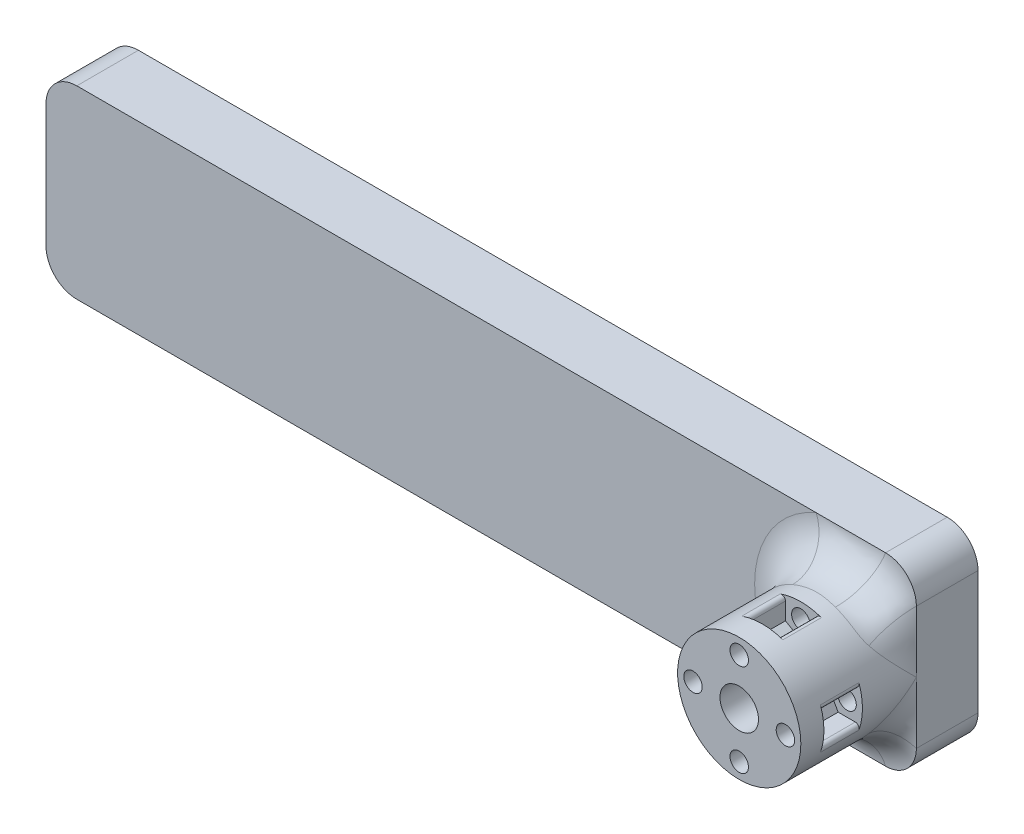
SolidWorks part; units mm, degrees
ref_plane "正面" through (0, 0, 0) normal (0, 0, 1) x (1, 0, 0)
ref_plane "平面" through (0, 0, 0) normal (0, 1, 0) x (1, 0, 0)
ref_plane "右側面" through (0, 0, 0) normal (1, 0, 0) x (0, 0, -1)
sketch "ｽｹｯﾁ1" plane through (0, 0, 0) normal (0, 0, 1) x (1, 0, 0)
  circle A1 centre (0, 0) radius 8
  dimension "D1" = 16
extrude "ﾎﾞｽ - 押し出し1" add sketch "ｽｹｯﾁ1" against normal blind 8
sketch "ｽｹｯﾁ24" plane through (0, 0, -8) normal (0, 0, -1) x (-1, 0, 0)
  line L0 (7.1547, 2) -> (8, 2)
  line L2 (7.1547, 2) -> (4.8453, 2)
  line L3 (4.8453, 2) -> (3.6906, 0)
  line L4 (3.6906, 0) -> (4.8453, -2)
  line L5 (4.8453, -2) -> (5.7854, -2)
  line L7 (8, 2) -> (8, -2)
  line L8 (8, -2) -> (5.7854, -2)
  line L10 (8.3094, 0) -> (7.1547, 2) [skipped]
  line L11 (7.1547, -2) -> (8.3094, 0) [skipped]
  circle A0 centre (6, 0) radius 2.25 construction
  circle A1 centre (0, 0) radius 8 construction
  dimension "D2" = 4.5
  dimension "D1" = 6
extrude "ｶｯﾄ - 押し出し10" cut sketch "ｽｹｯﾁ24" against normal blind 5
fillet "ﾌｨﾚｯﾄ2" radius 0.5 2 edges at (-7.746, -2, -5.5) (-7.746, 2, -5.5)
pattern_circular "円形ﾊﾟﾀｰﾝ1" count 4 over 360 about axis through (0, 0, -8) along (0, 0, 1) of "ｶｯﾄ - 押し出し10", "ﾌｨﾚｯﾄ2"
sketch "ｽｹｯﾁ25" plane through (0, 0, -8) normal (0, 0, -1) x (-1, 0, 0)
  circle A0 centre (0, 0) radius 8
extrude "ﾎﾞｽ - 押し出し6" add sketch "ｽｹｯﾁ25" along normal blind 7
hole_wizard "M4 すきま穴1" positions "ｽｹｯﾁ22" profile "ｽｹｯﾁ23" hole size "M4" standard "JIS"
sketch "ｽｹｯﾁ22" plane through (0, 0, 0) normal (0, 0, 1) x (1, 0, 0)
  point P0 (0, 0)
sketch "ｽｹｯﾁ23" plane through (0, 0, 0) normal (1, 0, 0) x (0, -1, 0)
  line L0 (0, 0) -> (0, 13.5022)
  line L1 (0, 13.5022) -> (2.5, 12)
  line L2 (2.5, 12) -> (2.5, 0)
  line L5 (2.5, 0) -> (0, 0)
  line L10 (0, 13.5022) -> (-2.5, 12) construction
  line L11 (0, -6.35) -> (0, 107.95) construction
  dimension "穴の直径" = 5
  dimension "穴の深さ" = 12
  dimension "ﾄﾞﾘﾙ角度" = 118
hole_wizard "M2 すきま穴1" positions "ｽｹｯﾁ26" profile "ｽｹｯﾁ27" hole size "M2" standard "JIS"
sketch "ｽｹｯﾁ26" plane through (0, 0, 0) normal (0, 0, 1) x (1, 0, 0)
  point P0 (6, 0)
  dimension "D1" = 6
sketch "ｽｹｯﾁ27" plane through (6, 0, 0) normal (1, 0, 0) x (0, -1, 0)
  line L0 (0, 0) -> (0, 15.721)
  line L1 (0, 15.721) -> (1.2, 15)
  line L2 (1.2, 15) -> (1.2, 0)
  line L5 (1.2, 0) -> (0, 0)
  line L10 (0, 15.721) -> (-1.2, 15) construction
  line L11 (0, -6.35) -> (0, 107.95) construction
  dimension "穴の直径" = 2.4
  dimension "穴の深さ" = 15
  dimension "ﾄﾞﾘﾙ角度" = 118
pattern_circular "円形ﾊﾟﾀｰﾝ2" count 4 every 90 about axis through (0, 0, 0) along (0, 0, 1) of "M2 すきま穴1"
sketch "ｽｹｯﾁ19" plane through (0, 0, -15) normal (0, 0, -1) x (-1, 0, 0)
  line L0 (-8, 8) -> (-8, -8)
  line L1 (-4, -12) -> (101, -12)
  line L2 (105, -8) -> (105, 8)
  line L3 (101, 12) -> (-4, 12)
  arc A0 (-8, -8) -> (-4, -12) centre (-4, -8) ccw
  arc A1 (101, -12) -> (105, -8) centre (101, -8) ccw
  arc A2 (105, 8) -> (101, 12) centre (101, 8) ccw
  arc A3 (-4, 12) -> (-8, 8) centre (-4, 8) ccw
  circle A5 centre (0, 0) radius 8 construction
  point P16 (-8, 0)
  dimension "D1" = 105
  dimension "D3" = 4
  dimension "D2" = 24
extrude "ﾎﾞｽ - 押し出し5" add sketch "ｽｹｯﾁ19" along normal blind 8
fillet "ﾌｨﾚｯﾄ1" radius 5 1 edges at (-8, 0, -15)
sketch "ｽｹｯﾁ20" plane through (0, 0, -23) normal (0, 0, -1) x (-1, 0, 0)
  line L1 (8, 8) -> (22.5, 8) construction
  line L2 (22.5, 8) -> (37, 8) construction
  line L3 (37, 8) -> (51.5, 8) construction
  line L4 (51.5, 8) -> (66, 8) construction
  line L5 (66, 8) -> (80.5, 8) construction
  line L6 (80.5, 8) -> (95, 8) construction
  line L7 (8, -8) -> (22.5, -8) construction
  line L8 (8, 0) -> (22.5, 0) construction
  line L9 (22.5, 0) -> (37, 0) construction
  line L10 (37, 0) -> (51.5, 0) construction
  line L11 (51.5, 0) -> (66, 0) construction
  line L12 (66, 0) -> (80.5, 0) construction
  line L13 (80.5, 0) -> (95, 0) construction
  line L14 (105, -8) -> (105, 8) construction
  line L16 (22.5, -8) -> (37, -8) construction
  line L17 (37, -8) -> (51.5, -8) construction
  line L18 (51.5, -8) -> (66, -8) construction
  line L19 (66, -8) -> (80.5, -8) construction
  line L20 (80.5, -8) -> (95, -8) construction
  line L21 (8, 8) -> (8, 0) construction
  line L22 (8, 0) -> (8, -8) construction
  line L23 (-8, 8) -> (-8, -8) construction
  circle A3 centre (37, 8) radius 3.2
  circle A4 centre (51.5, 8) radius 3.2
  circle A5 centre (66, 8) radius 3.2
  circle A6 centre (80.5, 8) radius 3.2
  circle A7 centre (95, 8) radius 3.2
  circle A11 centre (37, 0) radius 3.2
  circle A12 centre (51.5, 0) radius 3.2
  circle A13 centre (66, 0) radius 3.2
  circle A14 centre (80.5, 0) radius 3.2
  circle A15 centre (95, 0) radius 3.2
  circle A22 centre (37, -8) radius 3.2
  circle A23 centre (51.5, -8) radius 3.2
  circle A24 centre (66, -8) radius 3.2
  circle A25 centre (80.5, -8) radius 3.2
  circle A26 centre (95, -8) radius 3.2
  dimension "D1" = 45
  dimension "D3" = 6.4
  dimension "D2" = 10
extrude "ｶｯﾄ - 押し出し9" cut sketch "ｽｹｯﾁ20" against normal blind 3.2
